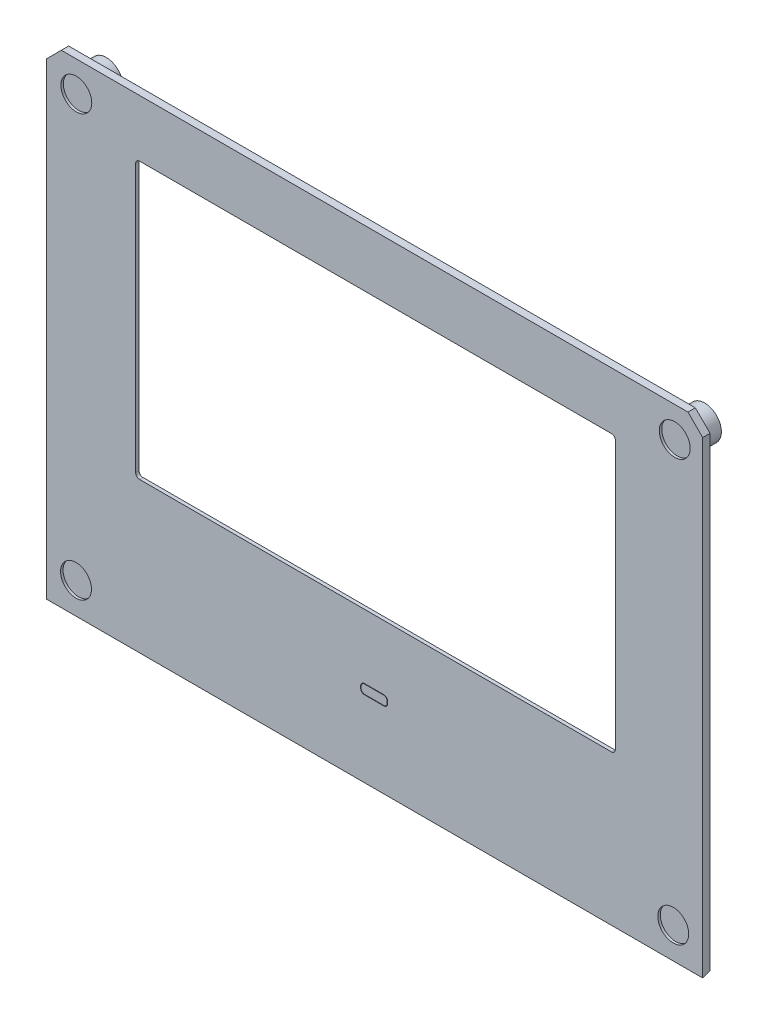
SolidWorks part; units mm, degrees
ref_plane "Front Plane" through (0, 0, 0) normal (0, 0, 1) x (1, 0, 0)
ref_plane "Top Plane" through (0, 0, 0) normal (0, 1, 0) x (1, 0, 0)
ref_plane "Right Plane" through (0, 0, 0) normal (1, 0, 0) x (0, 0, -1)
sketch "Sketch1" plane through (0, 0, 0) normal (0, 0, 1) x (1, 0, 0)
  line L0 (0, 0) -> (0, 2.5) construction
  line L2 (-49.5, -27) -> (49.5, -27)
  line L3 (-49.5, -27) -> (-49.5, 32)
  line L4 (-49.5, 32) -> (49.5, 32)
  line L5 (49.5, -27) -> (49.5, 32)
  line L6 (-49.5, -27) -> (49.5, 32) construction
  line L7 (-49.5, 32) -> (49.5, -27) construction
  line L16 (63.7, 42.2) -> (-64.0602, 42.2)
  line L17 (-64.0602, 42.2) -> (-67.0602, 39.2)
  line L18 (-67.0602, 39.2) -> (-67.0602, -42.1345)
  line L19 (-67.0602, -42.1345) -> (-67.0602, -55.3)
  line L20 (-67.0602, -55.3) -> (66.7, -55.3)
  line L21 (66.7, -55.3) -> (66.7, -42.1345)
  line L22 (66.7, -42.1345) -> (66.7, 39.2)
  line L23 (66.7, 39.2) -> (63.7, 42.2)
  point P14 (0, 0)
  dimension "D3" = 99
  dimension "D6" = 59
  dimension "D7" = 2.5
  dimension "D1" = 97.5
extrude "Boss-Extrude1" add sketch "Sketch1" along normal blind 1.5
sketch "Sketch2" plane through (-67.0602, 0, 0) normal (-1, 0, 0) x (0, 0, 1)
  line L1 (0, 39.2) -> (0, -55.3) construction
  line L2 (1.5684, -56.2492) -> (-60.7101, -33.5817)
  line L3 (1.5684, -56.2492) -> (-60.7101, -33.5817)
  line L4 (0, 39.2) -> (0, -55.3)
  line L5 (1.5, 39.2) -> (1.5, -55.3) construction
  line L6 (1.5, 39.2) -> (1.5, -55.3)
  line L7 (1.5, -55.3) -> (0, -55.3) construction
  line L8 (1.5, -55.3) -> (0, -55.3)
  line L9 (1.5, -55.3) -> (1.5, -56.4371)
  line L10 (0, -55.3) -> (0, -55.8912)
  line M3 (0, -55.3) -> (1.5, -55.3)
  dimension "D1" = 0.2
extrude "Boss-Extrude2" add sketch "Sketch2" against normal up to surface (133.7602 mm away) contours L10 L3 L9 M3 region at (-67.0602, -55.6447, 0.8548) up to face at (66.7, -8.05, 0.75)
sketch "Sketch3" plane through (0, 0, 0) normal (0, 0, -1) x (-1, 0, 0)
  line L0 (54.4999, -35.4999) -> (54.4999, 35.5001)
  line L1 (54.4999, 35.5001) -> (-54.5001, 35.5001)
  line L2 (-54.5001, 35.5001) -> (-54.5001, -35.4999)
  line L3 (-54.5001, -35.4999) -> (54.4999, -35.4999)
  line L4 (52.9999, -33.9999) -> (52.9999, 34.0001)
  line L5 (-53.0001, -33.9999) -> (52.9999, -33.9999)
  line L6 (-53.0001, 34.0001) -> (-53.0001, -33.9999)
  line L7 (52.9999, 34.0001) -> (-53.0001, 34.0001)
  line L8 (52.9999, -33.9999) -> (52.9999, 34.0001) construction
  line L9 (-53.0001, -33.9999) -> (52.9999, -33.9999) construction
  line L10 (-53.0001, 34.0001) -> (-53.0001, -33.9999) construction
  line L11 (52.9999, 34.0001) -> (-53.0001, 34.0001) construction
  dimension "D1" = 0
  dimension "D2" = 1.5
extrude "Cut-Extrude1" cut sketch "Sketch3" against normal blind 0.8
sketch "Sketch4" plane through (0, 0, 1.5) normal (0, 0, 1) x (1, 0, 0)
  circle A0 centre (60.7, -49.8912) radius 1.5 construction
  circle A1 centre (-61.0602, -49.8912) radius 1.5 construction
  circle A2 centre (60.7, -49.8912) radius 1.5
  circle A3 centre (-61.0602, -49.8912) radius 1.5
  spline S0 degree 3 poles (-62.625, 36) (-62.625, 32.75) (-59.375, 32.75) (-59.375, 36) (-59.375, 39.25) (-62.625, 39.25) (-62.625, 36) (-62.625, 32.75) (-59.375, 32.75) knots -0.5 0 0 0 0.5 0.5 0.5 1 1 1 1.5 1.5 1.5 weights 1 0.333333 0.333333 1 0.333333 0.333333 1 0.333333 0.333333 only from (-62.625, 36) to (-62.625, 36) construction
  spline S1 degree 3 poles (-62.625, 36) (-62.625, 32.75) (-59.375, 32.75) (-59.375, 36) (-59.375, 39.25) (-62.625, 39.25) (-62.625, 36) (-62.625, 32.75) (-59.375, 32.75) knots -0.5 0 0 0 0.5 0.5 0.5 1 1 1 1.5 1.5 1.5 weights 1 0.333333 0.333333 1 0.333333 0.333333 1 0.333333 0.333333 only from (-62.625, 36) to (-62.625, 36)
  spline S2 degree 3 poles (59.375, 36) (59.375, 32.75) (62.625, 32.75) (62.625, 36) (62.625, 39.25) (59.375, 39.25) (59.375, 36) (59.375, 32.75) (62.625, 32.75) knots -0.5 0 0 0 0.5 0.5 0.5 1 1 1 1.5 1.5 1.5 weights 1 0.333333 0.333333 1 0.333333 0.333333 1 0.333333 0.333333 only from (59.375, 36) to (59.375, 36) construction
  spline S3 degree 3 poles (59.375, 36) (59.375, 32.75) (62.625, 32.75) (62.625, 36) (62.625, 39.25) (59.375, 39.25) (59.375, 36) (59.375, 32.75) (62.625, 32.75) knots -0.5 0 0 0 0.5 0.5 0.5 1 1 1 1.5 1.5 1.5 weights 1 0.333333 0.333333 1 0.333333 0.333333 1 0.333333 0.333333 only from (59.375, 36) to (59.375, 36)
  spline S4 degree 3 poles (-62.625, -36) (-62.625, -39.25) (-59.375, -39.25) (-59.375, -36) (-59.375, -32.75) (-62.625, -32.75) (-62.625, -36) (-62.625, -39.25) (-59.375, -39.25) knots -0.5 0 0 0 0.5 0.5 0.5 1 1 1 1.5 1.5 1.5 weights 1 0.333333 0.333333 1 0.333333 0.333333 1 0.333333 0.333333 only from (-62.625, -36) to (-62.625, -36) construction
  spline S5 degree 3 poles (-62.625, -36) (-62.625, -39.25) (-59.375, -39.25) (-59.375, -36) (-59.375, -32.75) (-62.625, -32.75) (-62.625, -36) (-62.625, -39.25) (-59.375, -39.25) knots -0.5 0 0 0 0.5 0.5 0.5 1 1 1 1.5 1.5 1.5 weights 1 0.333333 0.333333 1 0.333333 0.333333 1 0.333333 0.333333 only from (-62.625, -36) to (-62.625, -36) construction
  spline S6 degree 3 poles (59.375, -36) (59.375, -39.25) (62.625, -39.25) (62.625, -36) (62.625, -32.75) (59.375, -32.75) (59.375, -36) (59.375, -39.25) (62.625, -39.25) knots -0.5 0 0 0 0.5 0.5 0.5 1 1 1 1.5 1.5 1.5 weights 1 0.333333 0.333333 1 0.333333 0.333333 1 0.333333 0.333333 only from (59.375, -36) to (59.375, -36) construction
  spline S7 degree 3 poles (59.375, -36) (59.375, -39.25) (62.625, -39.25) (62.625, -36) (62.625, -32.75) (59.375, -32.75) (59.375, -36) (59.375, -39.25) (62.625, -39.25) knots -0.5 0 0 0 0.5 0.5 0.5 1 1 1 1.5 1.5 1.5 weights 1 0.333333 0.333333 1 0.333333 0.333333 1 0.333333 0.333333 only from (59.375, -36) to (59.375, -36) construction
extrude "Cut-Extrude2" cut sketch "Sketch4" against normal blind 2
sketch "Sketch5" plane through (0, 0, 1.5) normal (0, 0, 1) x (1, 0, 0)
  line L4 (-57, 36) -> (-57, 40.2)
  line L5 (-57, 40.2) -> (-61, 40.2)
  line L6 (-65.2, 36) -> (-65.2, 32)
  line L7 (-65.2, 32) -> (-61, 32)
  line L8 (-57, 36) -> (-57, 40.2) construction
  line L9 (-57, 40.2) -> (-61, 40.2) construction
  line L10 (-65.2, 36) -> (-65.2, 32) construction
  line L11 (-65.2, 32) -> (-61, 32) construction
  line L12 (61, 40.2) -> (57, 40.2)
  line L13 (57, 40.2) -> (57, 36)
  line L14 (61, 32) -> (65.2, 32)
  line L15 (65.2, 32) -> (65.2, 36)
  line L16 (61, 40.2) -> (57, 40.2) construction
  line L17 (57, 40.2) -> (57, 36) construction
  line L18 (61, 32) -> (65.2, 32) construction
  line L19 (65.2, 32) -> (65.2, 36) construction
  circle A0 centre (-61, 36) radius 1.625 construction
  circle A1 centre (-61, 36) radius 1.625
  circle A2 centre (61, 36) radius 1.625 construction
  circle A3 centre (61, 36) radius 1.625
  arc A8 (-61, 40.2) -> (-65.2, 36) centre (-61.0002, 36.0002) ccw
  arc A9 (-61, 32) -> (-57, 36) centre (-61, 36) ccw
  arc A10 (-61, 40.2) -> (-65.2, 36) centre (-61.0002, 36.0002) ccw construction
  arc A11 (-61, 32) -> (-57, 36) centre (-61, 36) ccw construction
  arc A12 (65.2, 36) -> (61, 40.2) centre (61.0002, 36.0002) ccw
  arc A13 (57, 36) -> (61, 32) centre (61, 36) ccw
  arc A14 (65.2, 36) -> (61, 40.2) centre (61.0002, 36.0002) ccw construction
  arc A15 (57, 36) -> (61, 32) centre (61, 36) ccw construction
  circle A16 centre (-61, 36) radius 3.3998
  circle A17 centre (61.0002, 36.0002) radius 3.3998
  dimension "D3" = 0.8
  dimension "D1" = 0
  dimension "D2" = 0
extrude "Boss-Extrude3" add sketch "Sketch5" against normal offset from surface (6.1114 mm away) 1.7
sketch "Sketch6" plane through (0, 0, 1.5) normal (0, 0, 1) x (1, 0, 0)
  line L4 (3.5199, -36.2) -> (-11.8801, -36.2)
  line L5 (-11.8801, -36.2) -> (-11.8801, -48.2)
  line L6 (-11.8801, -48.2) -> (3.5199, -48.2)
  line L7 (3.5199, -48.2) -> (3.5199, -36.2)
  line L8 (3.5199, -36.2) -> (-11.8801, -36.2) construction
  line L9 (-11.8801, -36.2) -> (-11.8801, -48.2) construction
  line L10 (-11.8801, -48.2) -> (3.5199, -48.2) construction
  line L11 (3.5199, -48.2) -> (3.5199, -36.2) construction
  circle A0 centre (-0.2801, -39.7) radius 3.5
  circle A1 centre (-0.2801, -39.7) radius 2.5
  circle A2 centre (-0.2801, -39.7) radius 2.5 construction
  dimension "D3" = 7
  dimension "D1" = 0
  dimension "D2" = 0
extrude "Cut-Extrude5" cut sketch "Sketch6" against normal blind 10
sketch "Sketch7" plane through (0, 0, 1.5) normal (0, 0, 1) x (1, 0, 0)
  line L1 (-3.0301, -40.7) -> (2.4699, -40.7)
  line L2 (-3.0301, -40.7) -> (-3.0301, -38.7)
  line L3 (-3.0301, -38.7) -> (2.4699, -38.7)
  line L4 (2.4699, -40.7) -> (2.4699, -38.7)
  line L5 (-3.0301, -40.7) -> (2.4699, -38.7) construction
  line L6 (-3.0301, -38.7) -> (2.4699, -40.7) construction
  circle A0 centre (-0.2801, -39.7) radius 3.5 construction
  circle A1 centre (-0.2801, -39.7) radius 3.5
  dimension "D1" = 5.5
  dimension "D2" = 2
extrude "Boss-Extrude4" add sketch "Sketch7" against normal blind 0.8
fillet "Fillet1" radius 0.8 4 edges at (2.4699, -40.7, 1.1) (2.4699, -38.7, 1.1) (-3.0301, -40.7, 1.1) (-3.0301, -38.7, 1.1)
sketch "Sketch8" plane through (0, 0, 0.7) normal (0, 0, -1) x (-1, 0, 0)
  circle A0 centre (0.2801, -39.7) radius 3.25
  circle A1 centre (0.2801, -39.7) radius 3.5 construction
  dimension "D1" = 0.25
  dimension "D2" = 6.5
extrude "Boss-Extrude5" add sketch "Sketch8" along normal blind 1.5 separate body
sketch "Sketch9" plane through (0, 0, 0.7) normal (0, 0, 1) x (1, 0, 0)
  line L9 (2.3699, -39.9) -> (2.3699, -39.5)
  line L10 (-2.2301, -40.6) -> (1.6699, -40.6)
  line L11 (-2.9301, -39.5) -> (-2.9301, -39.9)
  line L12 (1.6699, -38.8) -> (-2.2301, -38.8)
  line L13 (2.3699, -39.9) -> (2.3699, -39.5)
  line L14 (-2.2301, -40.6) -> (1.6699, -40.6)
  line L15 (-2.9301, -39.5) -> (-2.9301, -39.9)
  line L16 (1.6699, -38.8) -> (-2.2301, -38.8)
  arc A8 (1.6699, -40.6) -> (2.3699, -39.9) centre (1.6699, -39.9) ccw
  arc A9 (-2.9301, -39.9) -> (-2.2301, -40.6) centre (-2.2301, -39.9) ccw
  arc A10 (-2.2301, -38.8) -> (-2.9301, -39.5) centre (-2.2301, -39.5) ccw
  arc A11 (2.3699, -39.5) -> (1.6699, -38.8) centre (1.6699, -39.5) ccw
  arc A12 (1.6699, -40.6) -> (2.3699, -39.9) centre (1.6699, -39.9) ccw
  arc A13 (-2.9301, -39.9) -> (-2.2301, -40.6) centre (-2.2301, -39.9) ccw
  arc A14 (-2.2301, -38.8) -> (-2.9301, -39.5) centre (-2.2301, -39.5) ccw
  arc A15 (2.3699, -39.5) -> (1.6699, -38.8) centre (1.6699, -39.5) ccw
  dimension "D1" = 0.1
extrude "Boss-Extrude6" add sketch "Sketch9" along normal up to surface (0.8 mm away) up to face at (-59.5602, -49.8912, 1.5)
sketch "Sketch10" plane through (0, 0, 1.5) normal (0, 0, 1) x (1, 0, 0)
  circle A0 centre (-61, 36) radius 3.15
  circle A1 centre (-61.0602, -49.8912) radius 3.15
  circle A2 centre (60.7, -49.8912) radius 3.15
  circle A3 centre (61, 36) radius 3.15
  dimension "D1" = 6.3
extrude "Cut-Extrude6" cut sketch "Sketch10" against normal blind 0.5
sketch "Sketch11" plane through (0, 0, 0) normal (0, 0, -1) x (-1, 0, 0)
  line L0 (-63.7, 42.2) -> (64.0602, 42.2) construction
  line L1 (67.0602, 39.2) -> (67.0602, -55.6784) construction
  line L2 (64.3998, 36) -> (64.3998, -2.317) construction
  line L3 (54.4999, -35.4999) -> (54.4999, 35.5001) construction
  line L4 (59.5602, 22.2) -> (59.5602, 29) construction
  circle A0 centre (59.5602, 22.2) radius 5.05 construction
  circle A1 centre (61, 36) radius 3.3998 construction
  circle A2 centre (62.6498, 16.1424) radius 1.75
  circle A3 centre (56.2499, 16.2602) radius 1.75
  circle A4 centre (59.5602, 29) radius 1.75
  spline S0 degree 3 poles (61, 39.3998) (54.2004, 39.3998) (54.2004, 32.6002) (61, 32.6002) (67.7996, 32.6002) (67.7996, 39.3998) (61, 39.3998) (54.2004, 39.3998) (54.2004, 32.6002) knots -0.5 0 0 0 0.5 0.5 0.5 1 1 1 1.5 1.5 1.5 weights 1 0.333333 0.333333 1 0.333333 0.333333 1 0.333333 0.333333 only from (61, 39.3998) to (61, 39.3998) construction
  dimension "D1" = 10.1
  dimension "D4" = 3.5
  dimension "D2" = 20
  dimension "D3" = 7.5
extrude "Boss-Extrude7" add sketch "Sketch11" along normal offset from surface (4.2114 mm away) 0.4 up to face at (-61, 39.3998, -4.6114)
sketch "Sketch12" plane through (0, 0, 1) normal (0, 0, 1) x (1, 0, 0)
  circle A0 centre (-61, 36) radius 1.625 construction
  circle A1 centre (-61, 36) radius 1.625
  circle A2 centre (-61.0602, -49.8912) radius 1.5 construction
  circle A3 centre (-61.0602, -49.8912) radius 1.5
  circle A4 centre (61, 36) radius 1.625 construction
  circle A5 centre (61, 36) radius 1.625
  circle A6 centre (60.7, -49.8912) radius 1.5 construction
  circle A7 centre (60.7, -49.8912) radius 1.5
extrude "Boss-Extrude8" add sketch "Sketch12" against normal blind 0.3
sketch "Sketch13" plane through (0, 0, 1.5) normal (0, 0, 1) x (1, 0, 0)
  line L1 (-49.5, 2.5) -> (49.5, 2.5) construction
  line L3 (-48.9, -25.6) -> (48.9, -25.6)
  line L4 (-48.9, -25.6) -> (-48.9, 30.6)
  line L5 (49.5, 32) -> (-49.5, 32)
  line L6 (49.5, -27) -> (49.5, 32)
  line L7 (-49.5, -27) -> (49.5, -27)
  line L8 (-49.5, 32) -> (-49.5, -27)
  line L9 (49.5, 32) -> (-49.5, 32)
  line L10 (49.5, -27) -> (49.5, 32)
  line L11 (-49.5, -27) -> (49.5, -27)
  line L12 (-49.5, 32) -> (-49.5, -27)
  line L13 (-48.9, 30.6) -> (48.9, 30.6)
  line L14 (48.9, -25.6) -> (48.9, 30.6)
  line L15 (-48.9, -25.6) -> (48.9, 30.6) construction
  line L16 (-48.9, 30.6) -> (48.9, -25.6) construction
  point P4 (0, 2.5)
  dimension "D2" = 1.4
  dimension "D3" = 0.6
  dimension "D1" = 0
extrude "Boss-Extrude9" add sketch "Sketch13" against normal up to surface (0.7 mm away) up to face at (0, 2.5, 0.8)
fillet "Fillet2" radius 0.8 4 edges at (-48.9, -25.6, 1.15) (-48.9, 30.6, 1.15) (48.9, 30.6, 1.15) (48.9, -25.6, 1.15)
